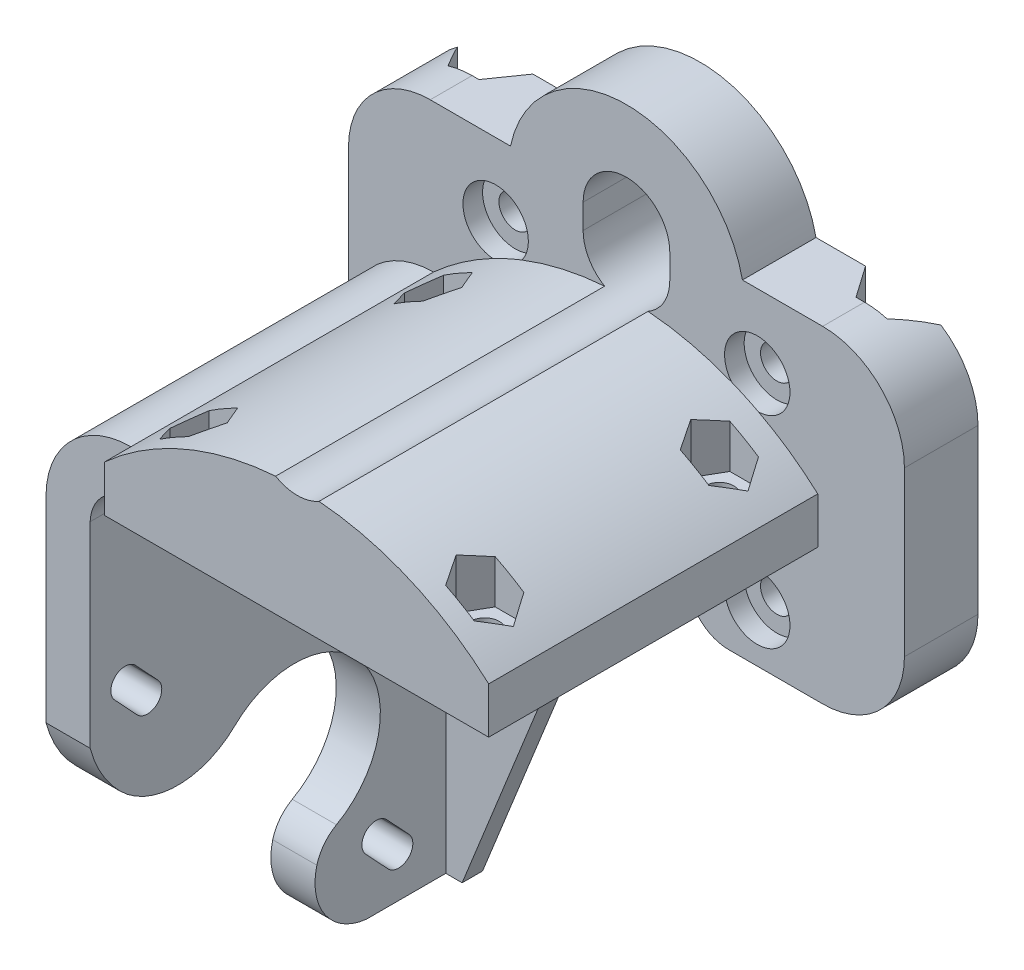
SolidWorks part; units mm, degrees
material "ABS"
ref_plane "Front Plane" through (0, 0, 0) normal (0, 0, 1) x (1, 0, 0)
ref_plane "Top Plane" through (0, 0, 0) normal (0, 1, 0) x (1, 0, 0)
ref_plane "Right Plane" through (0, 0, 0) normal (1, 0, 0) x (0, 0, -1)
sketch "Sketch1" plane through (0, 0, 0) normal (0, 0, 1) x (1, 0, 0)
  line L0 (-34, -20) -> (-7.5, -20)
  line L1 (-34, -20) -> (-34, 20)
  line L2 (34, -20) -> (34, 20)
  line L3 (-34, 20) -> (-14.1863, 20)
  line L4 (-34, -20) -> (34, 20) construction
  line L5 (34, -20) -> (-34, 20) construction
  line L6 (0, 18.5) -> (0, 15.5) construction
  line L7 (5.3, 18.5) -> (5.3, 15.5)
  line L8 (-5.3, 18.5) -> (-5.3, 15.5)
  line L10 (7.5, -13.5) -> (7.5, -20)
  line L11 (-7.5, -13.5) -> (-7.5, -20)
  line L12 (14.1863, 20) -> (34, 20)
  line L13 (7.5, -20) -> (34, -20)
  line L16 (-34, 0) -> (34, 0) construction
  line L17 (-34, -20) -> (-34, -67.5)
  line L18 (-34, -67.5) -> (-26.6, -67.5)
  line L19 (-26.6, -67.5) -> (-7.5, -20)
  arc A0 (14.1863, 20) -> (-14.1863, 20) centre (0, 17) ccw
  arc A1 (5.3, 18.5) -> (-5.3, 18.5) centre (0, 18.5) ccw
  arc A2 (-5.3, 15.5) -> (5.3, 15.5) centre (0, 15.5) ccw
  arc A3 (7.5, -13.5) -> (-7.5, -13.5) centre (0, -13.5) ccw
  circle A4 centre (-16, -13.7) radius 2
  circle A5 centre (16, -13.7) radius 2
  circle A6 centre (-16, 11) radius 2
  circle A7 centre (16, 11) radius 2
  point P1 (0, 0)
  point P10 (0, 17)
  dimension "D3" = 29
  dimension "D9" = 26.5
  dimension "D8" = 6.5
  dimension "D10" = 7.5
  dimension "D11" = 17
  dimension "D15" = 4
  dimension "D16" = 6.3
  dimension "D17" = 18
  dimension "D19" = 6.3
  dimension "D20" = 8.5
  dimension "D21" = 4
  dimension "D22" = 4
  dimension "D23" = 9
  dimension "D24" = 9
  dimension "D25" = 18
  dimension "D26" = 18
  dimension "D1" = 68
  dimension "D2" = 40
  dimension "D4" = 3
  dimension "D5" = 0
  dimension "D6" = 10.6
  dimension "D7" = 15
  dimension "D12" = 6.5
  dimension "D27" = 47.5
  dimension "D28" = 7.4
  dimension "D18" = 2
extrude "Boss-Extrude1" add sketch "Sketch1" along normal blind 6.5 and the other way blind 2.5 contours A3 L10 L13 L2 L12 A0 L3 L1 L0 L11 A7 A6 A5 A4 A2 L8 A1 L7 region at (0, 2.539, 0)
extrude "Boss-Extrude3" add sketch "Sketch1<5>" against normal blind 2.5 contours L18 L19 L0 L17 region at (-24.6282, -39.2896, 0)
sketch "Sketch1<5>" plane through (0, 0, 0) normal (0, 0, 1) x (1, 0, 0) same geometry as "Sketch1"
fillet "Fillet2" radius 10 3 edges at (34, -20, 2) (34, 20, 2) (-34, 20, 2)
sketch "Sketch2" plane through (0, 0, 6.5) normal (0, 0, 1) x (1, 0, 0)
  line L0 (34, -10) -> (34, 10) construction
  line L1 (23.4, 1.95) -> (-23.6, 1.95)
  line L2 (23.4, 1.95) -> (23.4, -3.7)
  line L3 (23.4, -3.7) -> (-23.6, -3.7)
  line L4 (-23.6, 1.95) -> (-23.6, -3.7)
  line L5 (-34, -20) -> (-7.5, -20) construction
  line L6 (-34, -20) -> (-28.6, -20)
  line L7 (-34, -67.5) -> (-28.6, -67.5)
  line L8 (-34, -67.5) -> (-34, -8.5)
  line L9 (-34, -8.5) -> (-28.6, -8.5)
  line L10 (-28.6, -67.5) -> (-28.6, -8.5)
  arc A0 (-23.6, 1.95) -> (23.4, 1.95) centre (-0.1, -23.9874) cw
  arc A1 (-23.6, 1.95) -> (-34, -8.5) centre (-23.5499, -8.5) ccw
  arc A2 (-23.6, -3.7) -> (-28.6, -8.5) centre (-23.604, -8.7) ccw
  line M13 (-34, 10) -> (-34, -20)
  line M14 (-34, -20) -> (-7.5, -20)
  arc M18 (5.3, 15.5) -> (-5.3, 15.5) centre (0, 15.5) cw
  dimension "D5" = 35
  dimension "D8" = 5
  dimension "D1" = 10.6
  dimension "D2" = 5.65
  dimension "D3" = 47
  dimension "D4" = 16.3
  dimension "D6" = 5.4
  dimension "D7" = 59
extrude "Boss-Extrude4" add sketch "Sketch2" along normal blind 40.25 contours L1 L4 L3 L2 | A0 L1 M18 region at (-0.1, -0.875, 6.5) region at (-0.1009, 5.5678, 6.5)
extrude "Boss-Extrude5" add sketch "Sketch2<4>" along normal blind 37 contours A2 L4 A1 L9 | L10 L9 M14 M13 region at (-28.6588, -3.3975, 6.5) region at (-31.3, -14.25, 6.5)
sketch "Sketch2<4>" plane through (0, 0, 6.5) normal (0, 0, 1) x (1, 0, 0) same geometry as "Sketch2"
extrude "Boss-Extrude6" add sketch "Sketch2<5>" along normal blind 37 and the other way blind 6.5 contours L7 L10 L8 M14 region at (-31.3, -43.75, 6.5)
sketch "Sketch2<5>" plane through (0, 0, 6.5) normal (0, 0, 1) x (1, 0, 0) same geometry as "Sketch2"
sketch "Sketch4" plane through (0, 0, 6.5) normal (0, 0, 1) x (1, 0, 0)
  circle A0 centre (-16, 11) radius 4
  circle A1 centre (16, 11) radius 4
  circle A2 centre (16, -13.7) radius 4
  circle A3 centre (-16, -13.7) radius 4
  dimension "D1" = 8
  dimension "D2" = 8
  dimension "D3" = 8
  dimension "D4" = 8
extrude "Cut-Extrude1" cut sketch "Sketch4" against normal blind 2.4
sketch "Sketch5" plane through (0, -3.7, 0) normal (0, -1, 0) x (-1, 0, 0)
  line L0 (24, -6.5) -> (14.1863, -6.5) construction
  line L1 (15.85, -15.5622) -> (19.35, -15.5622)
  line L2 (19.35, -15.5622) -> (21.1, -12.5311)
  line L3 (21.1, -12.5311) -> (19.35, -9.5)
  line L4 (19.35, -9.5) -> (15.85, -9.5)
  line L5 (15.85, -9.5) -> (14.1, -12.5311)
  line L6 (14.1, -12.5311) -> (15.85, -15.5622)
  line L7 (2.6645, -6.5) -> (12.7718, -6.5) construction
  line L8 (23.6, -43.5) -> (23.6, -6.5) construction
  circle A0 centre (17.6, -12.5311) radius 3.0311 construction
  circle A1 centre (17.6, -12.5311) radius 1.75
  dimension "D4" = 3.5
  dimension "D1" = 3.5
  dimension "D2" = 3
  dimension "D3" = 2.5
extrude "Cut-Extrude2" cut sketch "Sketch5" against normal through all contours A1
extrude "Cut-Extrude3" cut sketch "Sketch5<4>" against normal blind 12
sketch "Sketch5<4>" plane through (0, -3.7, 0) normal (0, -1, 0) x (-1, 0, 0) same geometry as "Sketch5"
extrude "Boss-Extrude7" add sketch "Sketch5<5>" against normal blind 5.65
sketch "Sketch5<5>" plane through (0, -3.7, 0) normal (0, -1, 0) x (-1, 0, 0) same geometry as "Sketch5"
pattern_linear "LPattern2" count 2 spacing 28.7 along (0, 0, 1) of "Boss-Extrude7", "Cut-Extrude3", "Cut-Extrude2"
ref_plane "Plane2" through (-0.1, 0, 0) normal (-1, 0, 0) x (0, 0, 1)
mirror "Mirror1" about plane through (-0.1, 0, 0) normal (-1, 0, 0) of "LPattern2"
sketch "Sketch7" plane through (-34, 0, 0) normal (-1, 0, 0) x (0, 0, 1)
  line L0 (-2.5, -67.5) -> (-2.5, 10) construction
  line L1 (-2.5, -67.5) -> (43.5, -67.5) construction
  line L3 (43.5, -8.5) -> (43.5, -67.5) construction
  circle A0 centre (18.5, -46.5) radius 10.5
  arc A1 (14.5, -56.2082) -> (9.7, -67.5) centre (8.9976, -60.5353) cw
  arc A2 (28.3467, -42.854) -> (43.5, -32.5) centre (29.9583, -28.9471) ccw
  point P6 (9.7, -67.5)
  point P7 (14.5, -56.2082)
  point P9 (28.3467, -42.854)
  point P10 (43.5, -32.5)
  line M1 (-2.5, -67.5) -> (43.5, -67.5)
  line M2 (43.5, -67.5) -> (43.5, -8.5)
  dimension "D1" = 21
  dimension "D2" = 21
  dimension "D3" = 21
  dimension "D6" = 17
  dimension "D7" = 7
  dimension "D8" = 15.1533
  dimension "D9" = 14
  dimension "D4" = 12.2
  dimension "D5" = 24
extrude "Cut-Extrude4" cut sketch "Sketch7" against normal blind 5.65 contours A2 A0 A1 M1 M2 | A0 region at (-34, -46.5, 18.5) region at (-34, -56.107, 32.326)
fillet "Fillet3" radius 10 1 edges at (-31.3, -42.854, 28.3467)
fillet "Fillet5" radius 5 1 edges at (-31.3, -56.2082, 14.5)
fillet "Fillet6" radius 5 1 edges at (7.5, -20, 2)
sketch "Sketch8" plane through (-7.5, 0, 0) normal (1, 0, 0) x (0, 0, -1)
  point P0 (0, -20)
fillet "Fillet12" radius 5 1 edges at (-7.5, -20, 3.25) tangent propagation no
sketch "Sketch10" plane through (-34, 0, 0) normal (-1, 0, 0) x (0, 0, 1)
  line L0 (5.6945, -28.2211) -> (8.6177, -30.9515) construction
  line L1 (6.8891, -26.9422) -> (9.8123, -29.6726)
  line L2 (4.5, -29.5) -> (7.4232, -32.2304)
  line L3 (36.4907, -30.6177) -> (39.2211, -27.6945) construction
  line L4 (35.2118, -29.4232) -> (37.9422, -26.5)
  line L5 (37.7696, -31.8123) -> (40.5, -28.8891)
  line L6 (8.5093, -59.3823) -> (5.7789, -62.3055) construction
  line L7 (9.7882, -60.5768) -> (7.0578, -63.5)
  line L8 (7.2304, -58.1877) -> (4.5, -61.1109)
  line L9 (-2.5, -67.5) -> (-2.5, 10) construction
  line L10 (-2.5, -67.5) -> (9.7, -67.5) construction
  line L11 (43.5, -8.5) -> (43.5, -32.5) construction
  line L12 (43.5, -8.5) -> (6.5, -8.5) construction
  arc A0 (6.8891, -26.9422) -> (4.5, -29.5) centre (5.6945, -28.2211) ccw
  arc A1 (7.4232, -32.2304) -> (9.8123, -29.6726) centre (8.6177, -30.9515) ccw
  arc A2 (35.2118, -29.4232) -> (37.7696, -31.8123) centre (36.4907, -30.6177) ccw
  arc A3 (40.5, -28.8891) -> (37.9422, -26.5) centre (39.2211, -27.6945) ccw
  arc A4 (9.7882, -60.5768) -> (7.2304, -58.1877) centre (8.5093, -59.3823) ccw
  arc A5 (4.5, -61.1109) -> (7.0578, -63.5) centre (5.7789, -62.3055) ccw
  point P2 (7.1561, -29.5863)
  point P7 (37.8559, -29.1561)
  point P14 (7.1441, -60.8439)
  dimension "D4" = 7
  dimension "D10" = 38
  dimension "D1" = 3.5
  dimension "D2" = 3.5
  dimension "D3" = 3.5
  dimension "D5" = 4
  dimension "D6" = 4
  dimension "D7" = 4
  dimension "D8" = 4
  dimension "D9" = 7
  dimension "D11" = 3
  dimension "D12" = 18
  dimension "D13" = 25.4008
extrude "Cut-Extrude5" cut sketch "Sketch10" against normal through all
sketch "Sketch11" plane through (0, 20, 0) normal (0, 1, 0) x (1, 0, 0)
  line L0 (29.4668, 2.5) -> (26.75, -1.38)
  line L1 (34, 2.5) -> (24, 2.5) construction
  line L2 (26.75, -1.38) -> (22.96, -1.38)
  line L3 (22.96, -1.38) -> (20.2432, 2.5)
  line L4 (14.1863, 2.5) -> (24, 2.5) construction
  line L5 (20.2432, 2.5) -> (29.4668, 2.5)
  line L6 (-0.1, 28.5845) -> (-0.1, -107.2042) construction
  line L7 (-0.1, 3.1075) -> (-0.1, -3.1075) construction
  line L8 (-20.4432, 2.5) -> (-29.6668, 2.5)
  line L9 (-23.16, -1.38) -> (-20.4432, 2.5)
  line L10 (-26.95, -1.38) -> (-23.16, -1.38)
  line L11 (-29.6668, 2.5) -> (-26.95, -1.38)
  dimension "D1" = 7.25
  dimension "D2" = 3.79
  dimension "D3" = 3.88
  dimension "D4" = 125
  dimension "D5" = 125
extrude "Cut-Extrude7" cut sketch "Sketch11" against normal up to vertex (40 mm away) up to point (24, -20, -2.5)
